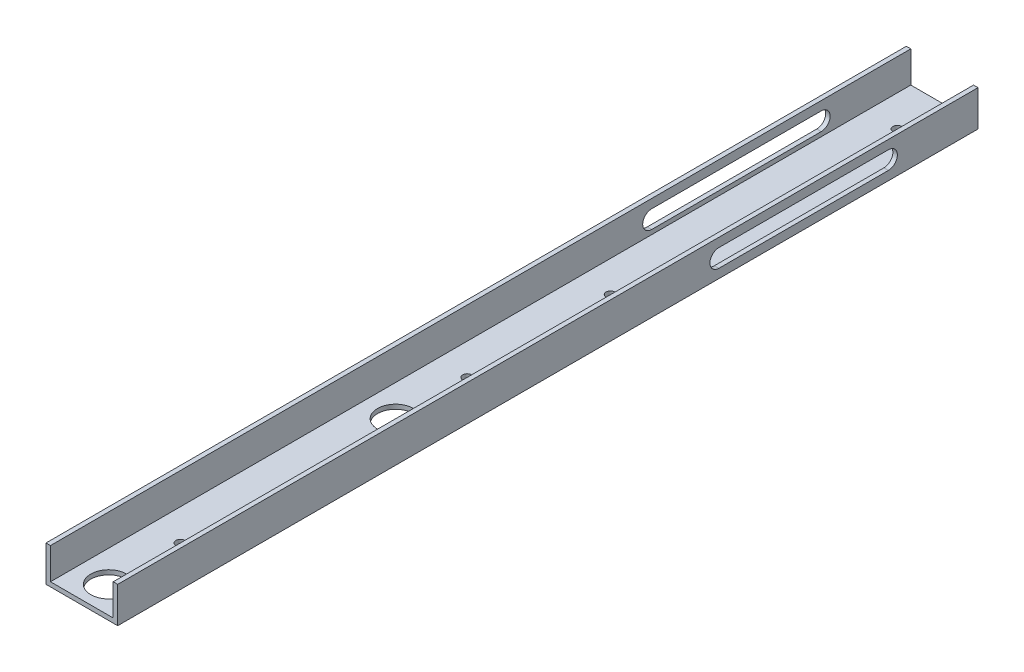
SolidWorks part; units mm, degrees
ref_plane "Front" through (0, 0, 0) normal (0, 0, 1) x (1, 0, 0)
ref_plane "Top" through (0, 0, 0) normal (0, 1, 0) x (1, 0, 0)
ref_plane "Right" through (0, 0, 0) normal (1, 0, 0) x (0, 0, -1)
sketch "Sketch1" plane through (0, 0, 0) normal (0, 0, 1) x (1, 0, 0)
  line L0 (47.625, 3.175) -> (47.625, 25.4)
  line L1 (0, 0) -> (50.8, 0)
  line L2 (0, 0) -> (0, 25.4)
  line L4 (50.8, 0) -> (50.8, 25.4)
  line L5 (3.175, 3.175) -> (47.625, 3.175)
  line L6 (3.175, 3.175) -> (3.175, 25.4)
  line L7 (50.8, 25.4) -> (47.625, 25.4)
  line L8 (0, 25.4) -> (3.175, 25.4)
  dimension "D1" = 25.4
  dimension "D2" = 50.8
  dimension "D3" = 3.175
extrude "Boss-Extrude1" add sketch "Sketch1" along normal blind 609.6
sketch "Sketch2" plane through (0, 3.175, 0) normal (0, 1, 0) x (1, 0, 0)
  line L0 (47.625, -609.6) -> (3.175, -609.6) construction
  circle A0 centre (25.4, -590.55) radius 12.7
  circle A1 centre (25.4, -387.35) radius 12.7
  circle A2 centre (25.4, -539.75) radius 3.175
  circle A3 centre (25.4, -336.55) radius 3.175
  dimension "D1" = 25.4
  dimension "D2" = 19.05
  dimension "D3" = 203.2
  dimension "D4" = 6.35
  dimension "D5" = 50.8
  dimension "D6" = 50.8
extrude "Cut-Extrude1" cut sketch "Sketch2" against normal up to next
sketch "Sketch3" plane through (0, 3.175, 0) normal (0, 1, 0) x (1, 0, 0)
  circle A0 centre (25.4, -234.95) radius 3.175
  circle A1 centre (25.4, -31.75) radius 3.175
  circle A2 centre (25.4, -387.35) radius 12.7 construction
  dimension "D1" = 6.35
  dimension "D2" = 203.2
  dimension "D3" = 152.4
extrude "Cut-Extrude2" cut sketch "Sketch3" against normal up to next
sketch "Sketch4" plane through (50.8, 0, 0) normal (1, 0, 0) x (0, 0, -1)
  line L0 (-63.5, 12.7) -> (-183.6067, 12.7) construction
  line L2 (-609.6, 25.4) -> (0, 25.4) construction
  line L3 (-183.6067, 12.7) -> (-63.5, 12.7) construction
  line L4 (-183.6067, 19.05) -> (-63.5, 19.05)
  line L5 (-183.6067, 6.35) -> (-63.5, 6.35)
  line L6 (0, 0) -> (0, 25.4) construction
  arc A0 (-183.6067, 19.05) -> (-183.6067, 6.35) centre (-183.6067, 12.7) ccw
  arc A1 (-63.5, 6.35) -> (-63.5, 19.05) centre (-63.5, 12.7) ccw
  point P2 (-123.5534, 12.7)
  point P9 (-203.7387, 12.7)
  dimension "D1" = 12.7
  dimension "D2" = 12.7
  dimension "D3" = 183.6067
  dimension "D4" = 63.5
extrude "Cut-Extrude3" cut sketch "Sketch4" against normal through all
